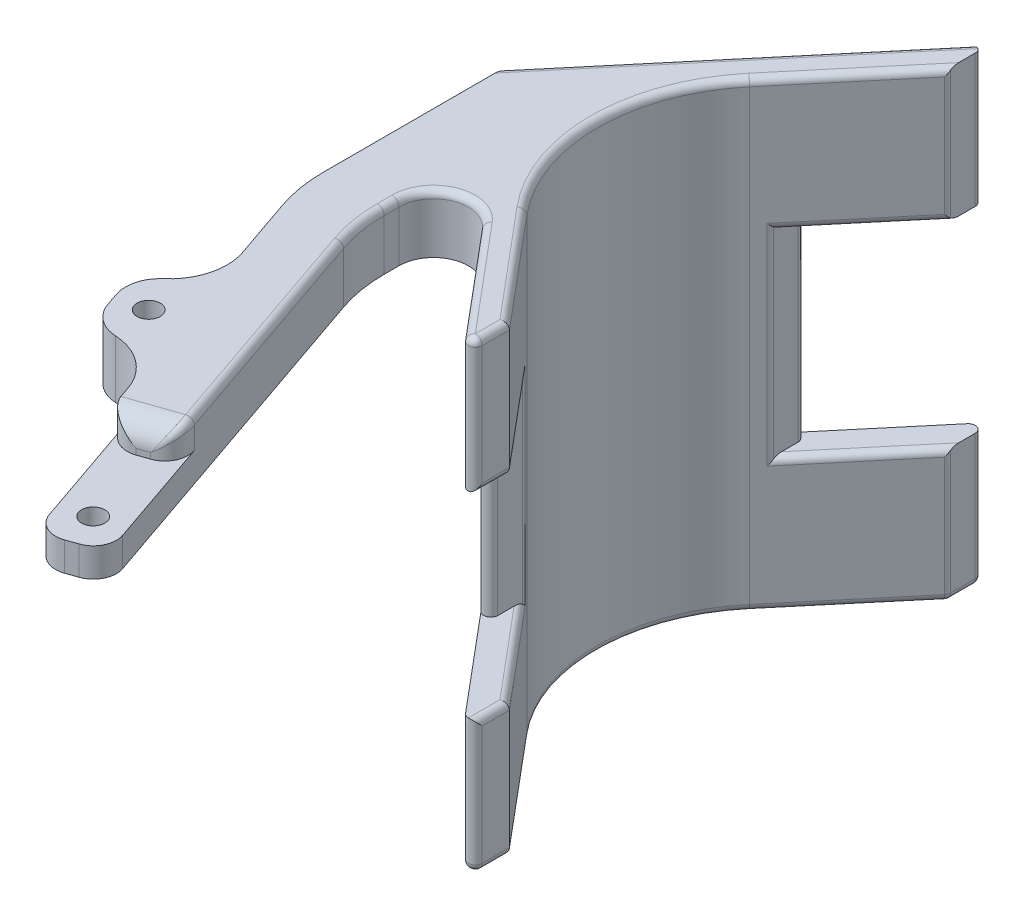
SolidWorks part; units mm, degrees
material "ABS"
ref_plane "Front Plane" through (0, 0, 0) normal (0, 0, 1) x (1, 0, 0)
ref_plane "Top Plane" through (0, 0, 0) normal (0, 1, 0) x (1, 0, 0)
ref_plane "Right Plane" through (0, 0, 0) normal (1, 0, 0) x (0, 0, -1)
sketch "Sketch1" plane through (0, 0, 0) normal (0, 1, 0) x (1, 0, 0)
  line L0 (0, 0) -> (40.4552, 48.2126)
  line L1 (40.4552, 48.2126) -> (40.4552, 58.3726)
  line L2 (40.4552, 58.3726) -> (-8.5253, 0)
  line L3 (0, 0) -> (110.068, 0) construction
  line L4 (40.4552, -48.2126) -> (40.4552, -58.3726)
  line L5 (40.4552, -58.3726) -> (-8.5253, 0)
  line L6 (0, 0) -> (40.4552, -48.2126)
  arc A0 (20.5497, 24.4902) -> (20.5497, -24.4902) centre (49.736, 0) ccw
  dimension "D1" = 38.1
  dimension "D2" = 50
  dimension "D3" = 10.16
  dimension "D4" = 76.2
extrude "Boss-Extrude1" add sketch "Sketch1" along normal mid plane 101.6 contours L2 L3 L0 L1 | L0 L3 A0 | L3 L6 A0 | L3 L5 L4 L6 region at (9.305, 0, 13.0589) region at (8.9625, 0, -6.4372) region at (8.9625, 0, 6.4372)
ref_plane "Plane1" through (-14.0282, 0, 38.5423) normal (-0.342, 0, 0.9397) x (0, -1, 0)
ref_plane "Plane2" through (0, 44.45, 0) normal (0, 1, 0) x (1, 0, 0)
sketch "Sketch7" plane through (0, 44.45, 0) normal (0, 1, 0) x (1, 0, 0)
  line L0 (21.8415, -133.9113) -> (6.9565, -90.6822)
  line L1 (21.8415, -133.9113) -> (33.8495, -129.7766)
  line L2 (33.8495, -129.7766) -> (4.9065, -45.72)
  line L3 (40.4552, -58.3726) -> (-8.5253, 0) construction
  line L4 (-8.5253, -45.72) -> (4.9065, -45.72)
  line L5 (1.9948, -76.2725) -> (-10.0133, -80.4072)
  line L6 (-10.0133, -80.4072) -> (-5.0516, -94.8169)
  line L7 (1.9948, -76.2725) -> (-8.5253, -45.72)
  line L8 (-5.0516, -94.8169) -> (6.9565, -90.6822)
  line L9 (-7.5324, -87.6121) -> (16.4837, -79.3426) construction
  line L10 (27.8455, -131.844) -> (-1.8094, -45.72) construction
  line L11 (-4.0092, -78.3399) -> (0.9524, -92.7496) construction
  line L12 (-8.5253, 0) -> (-8.5253, -45.72)
  line L13 (-8.5253, -45.72) -> (4.9065, -45.72)
  line L14 (4.9065, -45.72) -> (4.9065, -16.0074)
  line L15 (-8.5253, 0) -> (4.9065, -16.0074)
  circle A0 centre (25.3647, -124.6391) radius 2.5527
  circle A1 centre (-1.5284, -85.5447) radius 2.5527
  dimension "D6" = 5.1054
  dimension "D2" = 15.24
  dimension "D4" = 12.7
  dimension "D5" = 53.34
  dimension "D7" = 7.62
  dimension "D8" = 12.7
  dimension "D3" = 45.72
  dimension "D9" = 88.9
  dimension "D1" = 161
extrude "Boss-Extrude4" add sketch "Sketch7" along normal mid plane 12.7 contours L15 L12 L4 L14 | L6 L8 L0 L1 L2 L4 L7 L5 A1 A0 region at (10.8573, 44.45, 87.8008) region at (-2.2844, 44.45, 26.5788)
fillet "Fillet2" radius 12.7 2 edges at (1.9948, 44.45, 76.2725) (6.9565, 44.45, 90.6822)
fillet "Fillet3" radius 7.62 2 edges at (-10.0133, 44.45, 80.4072) (-5.0516, 44.45, 94.8169)
fillet "Fillet4" radius 7.62 1 edges at (4.9065, 44.45, 16.0074)
fillet "Fillet5" radius 33.02 2 edges at (4.9065, 44.45, 45.72) (-8.5253, 44.45, 45.72)
sketch "Sketch9" plane through (40.4552, 0, 0) normal (1, 0, 0) x (0, 0, -1)
  line L0 (58.3726, 50.8) -> (58.3726, -50.8) construction
  line L1 (-58.3726, 21.59) -> (58.3726, 21.59)
  line L2 (-58.3726, 21.59) -> (-58.3726, -21.59)
  line L3 (-58.3726, -21.59) -> (58.3726, -21.59)
  line L4 (58.3726, 21.59) -> (58.3726, -21.59)
  line L5 (-58.3726, 21.59) -> (58.3726, -21.59) construction
  line L6 (-58.3726, -21.59) -> (58.3726, 21.59) construction
  point P0 (0, 0)
  dimension "D1" = 43.18
extrude "Cut-Extrude2" cut sketch "Sketch9" against normal blind 17.78
sketch "Sketch10" plane through (0, 50.8, 0) normal (0, -1, 0) x (1, 0, 0)
  line L0 (21.8415, 133.9113) -> (11.0912, 102.6903) construction
  line L1 (21.8415, 133.9113) -> (33.8495, 129.7766) construction
  line L2 (33.8495, 129.7766) -> (6.7055, 50.9446) construction
  line L3 (21.8415, 133.9113) -> (11.0912, 102.6903)
  line L4 (21.8415, 133.9113) -> (33.8495, 129.7766)
  line L5 (33.8495, 129.7766) -> (6.7055, 50.9446)
  line L6 (13.572, 109.8951) -> (25.5801, 105.7604)
  line M22 (33.8495, 129.7766) -> (6.7055, 50.9446)
  line M33 (21.8415, 133.9113) -> (33.8495, 129.7766)
  circle M35 centre (25.3647, 124.6391) radius 2.5527
extrude "Cut-Extrude3" cut sketch "Sketch10" along normal blind 6.35 contours L6 L3 M33 M22 M35 region at (23.5987, 50.8, 119.5104)
fillet "Fillet7" radius 1.524 33 edges at (30.5024, -50.8, -36.3514) (30.5024, -50.8, 36.3514) (30.5024, 50.8, -36.3514) (11.636, 50.8, 0) (15.965, -50.8, 29.1863) (15.965, -50.8, -29.1863) (15.965, 50.8, -29.1863) (29.4095, 50.8, 45.2088) (40.4552, 36.195, -48.2126) (22.6752, 0, -27.0232) (31.5652, 21.59, -37.6179) (31.5652, -21.59, -37.6179) (40.4552, -50.8, -53.2926) (40.4552, -36.195, -48.2126) (40.4552, 21.59, 53.2926) (31.5652, 21.59, 37.6179) (22.6752, 0, 27.0232) (31.5652, -21.59, 37.6179) (40.4552, -21.59, 53.2926) (40.4552, -50.8, 53.2926) (11.636, -50.8, 0) (40.4552, 50.8, 53.2926) (30.5024, 50.8, 36.3514) (22.6752, 0, -37.1832) (22.6752, 0, 37.1832) (40.4552, -36.195, 58.3726) (40.4552, -36.195, -58.3726) (40.4552, 36.195, -58.3726) (40.4552, 36.195, 58.3726) (16.1428, 50.8, 78.3525) (5.3594, 50.8, 45.6442) (4.9065, 50.8, 38.5688) (9.9203, 50.8, 29.7827)
fillet "Fillet8" radius 5.08 6 edges at (33.8495, 41.275, 129.7766) (21.8415, 41.275, 133.9113) (25.5801, 46.863, 105.7604) (13.572, 47.625, 109.8951) (18.8556, 50.8, 108.0759) (25.1581, 50.3536, 105.9058)
equation "\"grabbing radius\"= 1.5in"
equation "\"grabbing height\"= 4in"
equation "\"sidewall thickness\"= 0.4in"
equation "\"D1@Sketch1\"=\"grabbing radius\""
equation "\"D3@Sketch1\"=\"sidewall thickness\""
equation "\"D1@Boss-Extrude1\"=\"grabbing height\""
equation "\"linkage thickness\"= .5in"
equation "\"D1@Boss-Extrude4\"=\"linkage thickness\""
equation "\"D1@Cut-Extrude3\"=\"linkage thickness\"/2"
equation "\"open angle\"= 50deg"
equation "\"D2@Sketch1\"=\"open angle\""
equation "\"tilt angle\"= 161deg"
equation "\"linkage hole axial offset\"= 2.1'Offset along the length of the arm"
equation "\"D5@Sketch7\"=\"linkage hole axial offset\""
equation "\"D1@Sketch7\"=\"tilt angle\""
equation "\"finger length\"= 3in "
equation "\"hinge cutout\"= 1in"
equation "\"D1@Sketch10\"=\"hinge cutout\""
